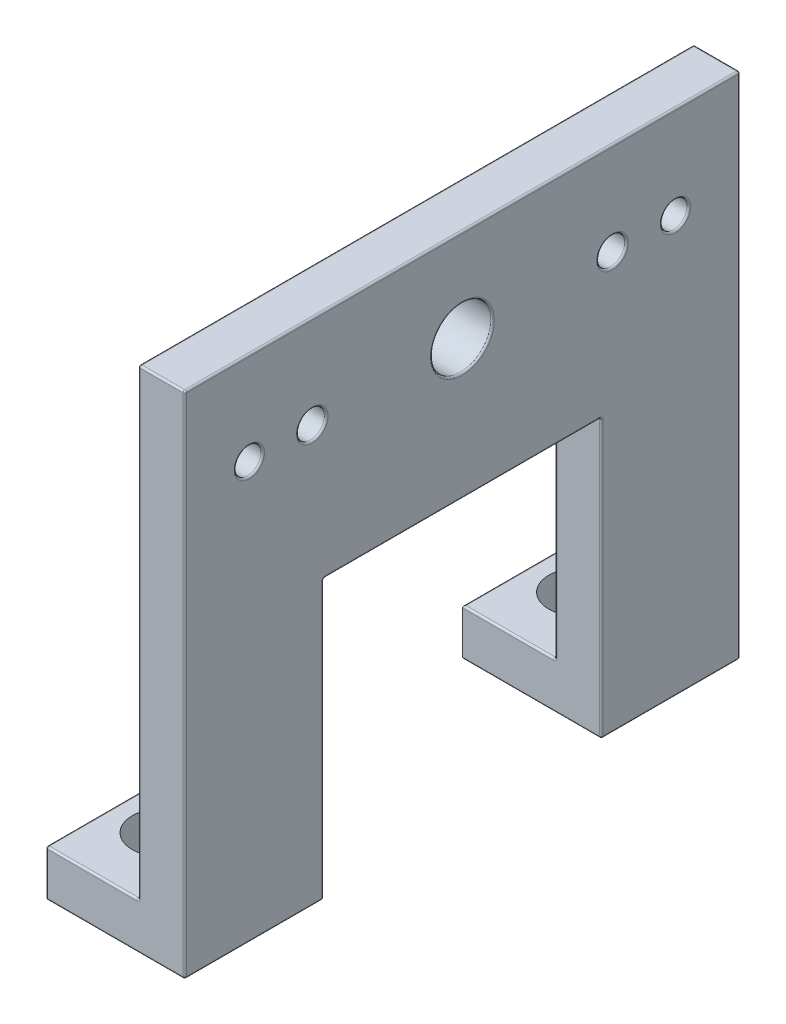
SolidWorks part; units mm, degrees
ref_plane "Front Plane" through (0, 0, 0) normal (0, 0, 1) x (1, 0, 0)
ref_plane "Top Plane" through (0, 0, 0) normal (0, 1, 0) x (1, 0, 0)
ref_plane "Right Plane" through (0, 0, 0) normal (1, 0, 0) x (0, 0, -1)
sketch "Sketch1" plane through (0, 0, 0) normal (0, 0, 1) x (1, 0, 0)
  line L1 (0, 0) -> (15, 0)
  line L2 (0, 0) -> (0, 5)
  line L3 (0, 5) -> (10, 5)
  line L6 (12.5, 0) -> (12.5, 55) construction
  line L7 (15, 55) -> (10, 55)
  line L8 (10, 5) -> (10, 55)
  line L10 (15, 5) -> (15, 55)
  line L11 (15, 5) -> (15, 0)
  dimension "D1" = 5
  dimension "D2" = 5
  dimension "D3" = 50
  dimension "D4" = 15
extrude "Boss-Extrude1" add sketch "Sketch1" along normal blind 60
sketch "Sketch2" plane through (15, 0, 0) normal (1, 0, 0) x (0, 0, -1)
  line L4 (0, 0) -> (0, 55)
  line L5 (0, 55) -> (-60, 55)
  line L6 (-60, 55) -> (-60, 0)
  line L7 (-60, 0) -> (0, 0)
  line L8 (0, 0) -> (0, 55) construction
  line L9 (0, 55) -> (-60, 55) construction
  line L10 (-60, 55) -> (-60, 0) construction
  line L12 (0, 0) -> (0, 55)
  line L13 (0, 55) -> (-60, 55)
  line L14 (-60, 55) -> (-60, 0)
  line L15 (-60, 0) -> (0, 0)
  line L20 (0, 0) -> (0, 55) construction
  line L21 (0, 55) -> (-60, 55) construction
  line L22 (-60, 55) -> (-60, 0) construction
  line L23 (-60, 0) -> (0, 0) construction
  circle A0 centre (-30, 45) radius 3.25
  circle A1 centre (-53.0125, 45) radius 1.435 construction
  circle A2 centre (-46.215, 45) radius 1.5 construction
  circle A3 centre (-13.785, 45) radius 1.5 construction
  circle A4 centre (-6.9875, 45) radius 1.435 construction
  circle A5 centre (-53.0125, 45) radius 1.435
  circle A6 centre (-46.215, 45) radius 1.5
  circle A7 centre (-13.785, 45) radius 1.5
  circle A8 centre (-6.9875, 45) radius 1.435
  point P2 (-30, 55)
  point P4 (-60, 27.5)
  point P6 (-30, 45)
  dimension "D4" = 6.5
  dimension "D2" = 0
  dimension "D3" = 10
  dimension "D1" = 0
extrude "Cut-Extrude1" cut sketch "Sketch2" against normal through all
sketch "Sketch3" plane through (0, 0, 0) normal (0, 0, -1) x (-1, 0, 0)
  line L0 (-15, 30) -> (-10, 30)
  line L6 (0, 0) -> (0, 5)
  line L7 (0, 5) -> (-10, 5)
  line L8 (-10, 5) -> (-10, 55)
  line L9 (-10, 55) -> (-15, 55)
  line L10 (-15, 55) -> (-15, 0)
  line L11 (-15, 0) -> (0, 0)
  line L12 (0, 0) -> (0, 5)
  line L13 (0, 5) -> (-10, 5)
  line L14 (-10, 5) -> (-10, 30)
  line L16 (-15, 30) -> (-15, 0)
  line L17 (-15, 0) -> (0, 0)
  dimension "D2" = 30
  dimension "D1" = 0
extrude "Cut-Extrude2" cut sketch "Sketch3" against normal blind 30 from offset 15 offset against normal yes
fillet "Fillet16" radius 0.2 44 edges at (5, 5, 15) (0, 5, 7.5) (0, 5, 52.5) (5, 5, 45) (12.5, 30, 45) (12.5, 30, 15) (0, 0, 52.5) (7.5, 0, 45) (0, 0, 7.5) (7.5, 0, 15) (5, 5, 60) (12.5, 55, 60) (7.5, 0, 60) (0, 2.5, 60) (7.5, 0, 0) (12.5, 55, 0) (5, 5, 0) (0, 2.5, 0) (15, 0, 52.5) (15, 27.5, 60) (15, 55, 30) (15, 27.5, 0) (15, 0, 7.5) (15, 15, 15) (15, 30, 30) (15, 15, 45) (15, 46.435, 6.9875) (15, 46.5, 13.785) (15, 46.5, 46.215) (15, 46.435, 53.0125) (15, 48.25, 30) (10, 30, 30) (10, 17.5, 15) (10, 5, 7.5) (10, 30, 0) (10, 55, 30) (10, 30, 60) (10, 5, 52.5) (10, 17.5, 45) (10, 46.435, 6.9875) (10, 46.5, 13.785) (10, 46.5, 46.215) (10, 46.435, 53.0125) (10, 48.25, 30)
sketch "Sketch4" plane through (0, 5, 0) normal (0, 1, 0) x (1, 0, 0)
  line L4 (0.2, -0.2) -> (0.2, -14.8)
  line L5 (0.2, -14.8) -> (9.8, -14.8)
  line L6 (9.8, -14.8) -> (9.8, -0.2)
  line L7 (9.8, -0.2) -> (0.2, -0.2)
  line L8 (0.2, -0.2) -> (0.2, -14.8) construction
  line L9 (0.2, -14.8) -> (9.8, -14.8) construction
  line L10 (9.8, -14.8) -> (9.8, -0.2) construction
  line L11 (9.8, -0.2) -> (0.2, -0.2) construction
  line L12 (9.8, -45.2) -> (0.2, -45.2)
  line L13 (0.2, -45.2) -> (0.2, -59.8)
  line L14 (0.2, -59.8) -> (9.8, -59.8)
  line L15 (9.8, -59.8) -> (9.8, -45.2)
  line L16 (9.8, -45.2) -> (0.2, -45.2) construction
  line L17 (0.2, -45.2) -> (0.2, -59.8) construction
  line L18 (0.2, -59.8) -> (9.8, -59.8) construction
  line L19 (9.8, -59.8) -> (9.8, -45.2) construction
  circle A0 centre (5, -7.5) radius 3.175
  circle A1 centre (5, -52.5) radius 3.175
  point P6 (9.8, -7.5)
  point P8 (5, -0.2)
  point P10 (9.8, -52.5)
  point P11 (5, -45.2)
  dimension "D3" = 6.35
  dimension "D1" = 0
  dimension "D2" = 0
extrude "Cut-Extrude3" cut sketch "Sketch4" against normal through all
